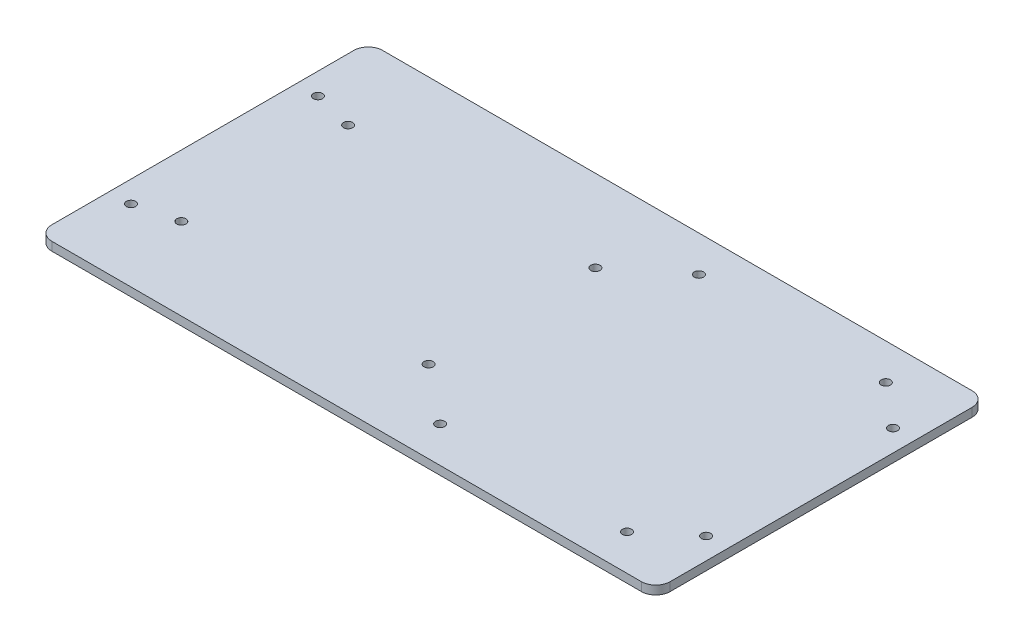
SolidWorks part; units mm, degrees
ref_plane "Front Plane" through (0, 0, 0) normal (0, 0, 1) x (1, 0, 0)
ref_plane "Top Plane" through (0, 0, 0) normal (0, 1, 0) x (1, 0, 0)
ref_plane "Right Plane" through (0, 0, 0) normal (1, 0, 0) x (0, 0, -1)
sketch "Sketch1" plane through (0, 0, 0) normal (0, 1, 0) x (1, 0, 0)
  line L0 (107.5, 0) -> (-107.5, 0) construction
  line L1 (-107.5, -57.5) -> (107.5, -57.5)
  line L2 (-107.5, -57.5) -> (-107.5, 57.5)
  line L3 (-107.5, 57.5) -> (107.5, 57.5)
  line L4 (107.5, -57.5) -> (107.5, 57.5)
  line L5 (-107.5, -57.5) -> (107.5, 57.5) construction
  line L6 (-107.5, 57.5) -> (107.5, -57.5) construction
  line L7 (0, -57.5) -> (0, 57.5) construction
  circle A0 centre (100, -32.5) radius 1.6
  circle A1 centre (-100, -32.5) radius 1.6
  circle A2 centre (100, 32.5) radius 1.6
  circle A3 centre (-100, 32.5) radius 1.6
  circle A4 centre (-86, 29) radius 1.6
  circle A5 centre (0, 29) radius 1.6
  circle A6 centre (0, -29) radius 1.6
  circle A7 centre (-86, -29) radius 1.6
  circle A9 centre (20, 45) radius 1.6
  circle A10 centre (85, 45) radius 1.6
  circle A11 centre (85, -45) radius 1.6
  circle A12 centre (20, -45) radius 1.6
  point P0 (0, 0)
  dimension "D3" = 3.2
  dimension "D6" = 3.2
  dimension "D9" = 3.2
  dimension "D11" = 3.2
  dimension "D12" = 3.2
  dimension "D1" = 115
  dimension "D2" = 215
  dimension "D4" = 7.5
  dimension "D5" = 25
  dimension "D7" = 29
  dimension "D10" = 86
  dimension "D13" = 65
  dimension "D14" = 20
  dimension "D15" = 45
extrude "Boss-Extrude1" add sketch "Sketch1" along normal blind 3
fillet "Fillet1" radius 5 4 edges at (-107.5, 1.5, -57.5) (107.5, 1.5, -57.5) (107.5, 1.5, 57.5) (-107.5, 1.5, 57.5)
